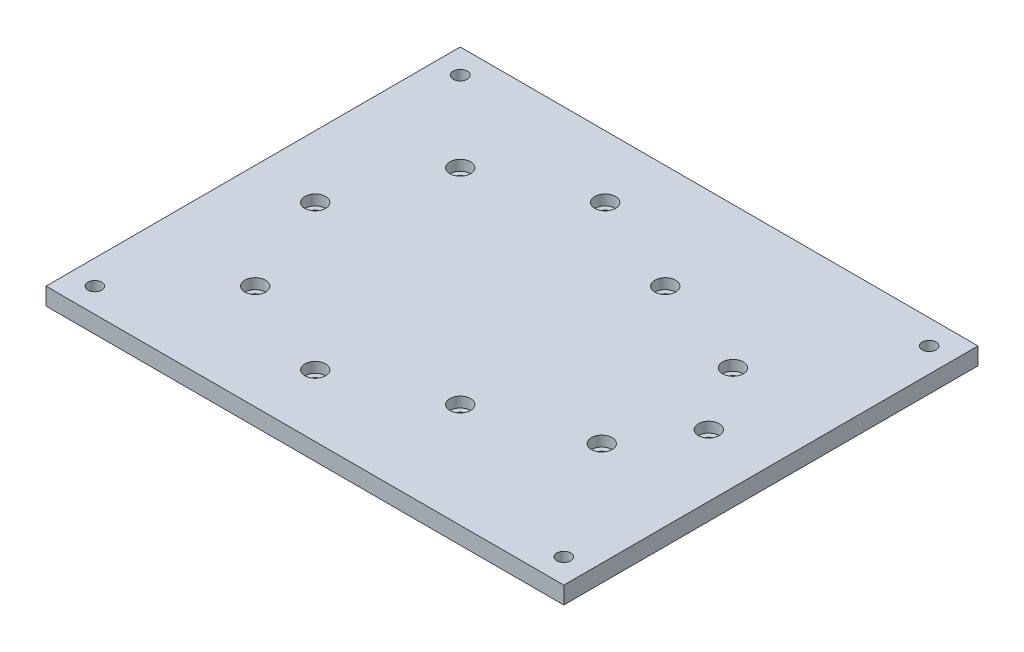
SolidWorks part; units mm, degrees
ref_plane "Front Plane" through (0, 0, 0) normal (0, 0, 1) x (1, 0, 0)
ref_plane "Top Plane" through (0, 0, 0) normal (0, 1, 0) x (1, 0, 0)
ref_plane "Right Plane" through (0, 0, 0) normal (1, 0, 0) x (0, 0, -1)
sketch "Sketch1" plane through (0, 0, 0) normal (0, 1, 0) x (1, 0, 0)
  line L8 (45, 0) -> (57, 0) construction
  line L16 (-15, 0) -> (-32, 0) construction
  line L17 (45, 19) -> (45, -19) construction
  line L18 (-75, -60) -> (-75, 60)
  line L19 (-75, 60) -> (75, 60)
  line L20 (75, 60) -> (75, -60)
  line L21 (75, -60) -> (-75, -60)
  line L22 (-15, 0) -> (14.6985, 29.6985) construction
  line L23 (-75, 60) -> (-67.9289, 52.9289) construction
  line L24 (75, -60) -> (67.9289, -52.9289) construction
  line L26 (-15, 0) -> (9, 0) construction
  line L27 (-15, -16) -> (-15, 16) construction
  circle A8 centre (-15, 0) radius 57 construction
  circle A27 centre (-15, 0) radius 42 construction
  circle A28 centre (14.6985, 29.6985) radius 1.55
  circle A29 centre (-15, 42) radius 1.55
  circle A30 centre (-44.6985, 29.6985) radius 1.55
  circle A31 centre (-57, 0) radius 1.55
  circle A32 centre (-44.6985, -29.6985) radius 1.55
  circle A33 centre (-15, -42) radius 1.55
  circle A34 centre (14.6985, -29.6985) radius 1.55
  circle A38 centre (45, 0) radius 27 construction
  circle A39 centre (45, -19) radius 1.55
  circle A40 centre (57, 0) radius 1.55
  circle A41 centre (45, 19) radius 1.55
  circle A42 centre (-67.9289, 52.9289) radius 2.05
  circle A43 centre (67.9289, -52.9289) radius 2
  circle A44 centre (-67.9289, -52.9289) radius 2
  circle A45 centre (67.9289, 52.9289) radius 2
  point P17 (45, 0)
  point P25 (-15, 0)
  point P28 (-15, 0)
  point P31 (-15, 0)
  point P36 (-15, 0)
  point P39 (-32, 0)
  point P53 (-15, 0)
  point P67 (-15, 0)
  dimension "D1" = 7
extrude "Boss-Extrude1" add sketch "Sketch1" along normal blind 5
sketch "Sketch2" plane through (0, 5, 0) normal (0, 1, 0) x (1, 0, 0)
  circle A0 centre (14.6985, 29.6985) radius 3
  circle A1 centre (-15, 42) radius 3
  circle A2 centre (-44.6985, 29.6985) radius 3
  circle A3 centre (-57, 0) radius 3
  circle A4 centre (-44.6985, -29.6985) radius 3
  circle A5 centre (-15, -42) radius 3
  circle A6 centre (14.6985, -29.6985) radius 3
  circle A10 centre (45, -19) radius 3
  circle A11 centre (57, 0) radius 3
  circle A12 centre (45, 19) radius 3
  point P5 (-15, 0)
  point P19 (-15, 0)
  dimension "D1" = 7
extrude "Cut-Extrude1" cut sketch "Sketch2" against normal blind 3
